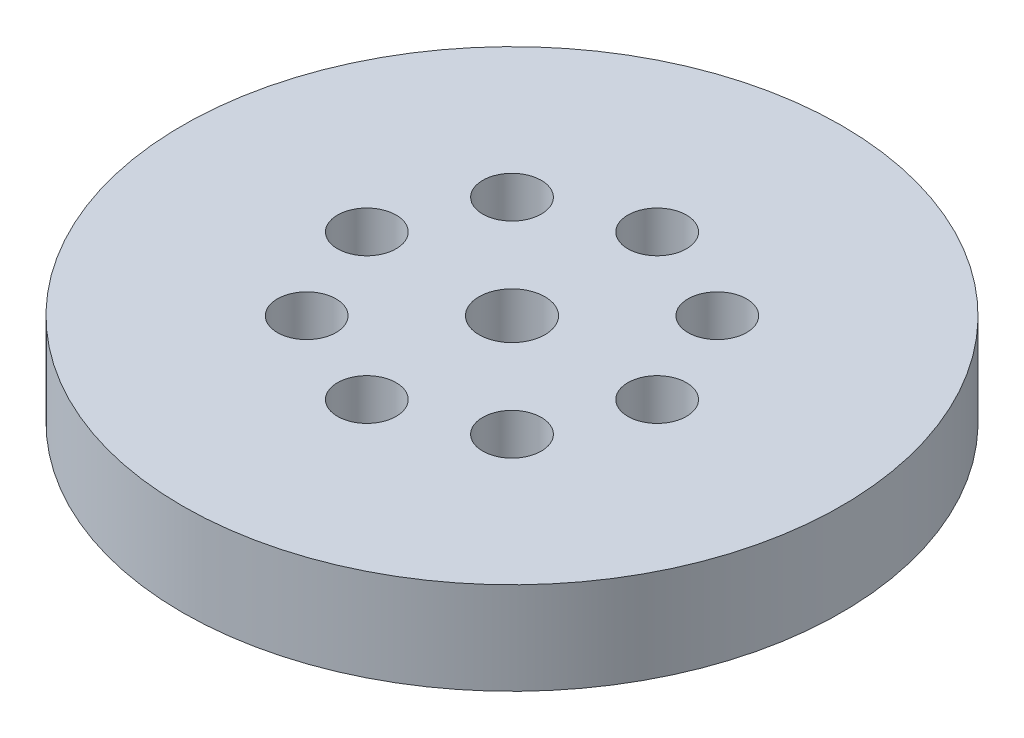
SolidWorks part; units mm, degrees
ref_plane "Front Plane" through (0, 0, 0) normal (0, 0, 1) x (1, 0, 0)
ref_plane "Top Plane" through (0, 0, 0) normal (0, 1, 0) x (1, 0, 0)
ref_plane "Right Plane" through (0, 0, 0) normal (1, 0, 0) x (0, 0, -1)
sketch "Sketch1" plane through (0, 0, 0) normal (0, 1, 0) x (1, 0, 0)
  circle A0 centre (0, 0) radius 100
  dimension "FLANGE_OD" = 200
extrude "Boss-Extrude1" add sketch "Sketch1" along normal blind 28
sketch "Sketch2" plane through (0, 0, 0) normal (0, 1, 0) x (1, 0, 0)
  circle A0 centre (0, 0) radius 10
  dimension "BORE_D" = 20
extrude "Cut-Extrude1" cut sketch "Sketch2" along normal through all
sketch "Sketch3" plane through (0, 28, 0) normal (0, 1, 0) x (1, 0, 0)
  circle A0 centre (0, 0) radius 44.0475 construction
  circle A1 centre (-44.0475, 0) radius 8.8861
  dimension "BOLT_D" = 17.7722
  dimension "BOLT_PCD" = 88.095
extrude "Cut-Extrude2" cut sketch "Sketch3" against normal blind 19.8625
pattern_circular "CirPattern1" count 8 over 360 about axis through (0, 0, 0) along (0, 1, 0) of "Cut-Extrude2"
